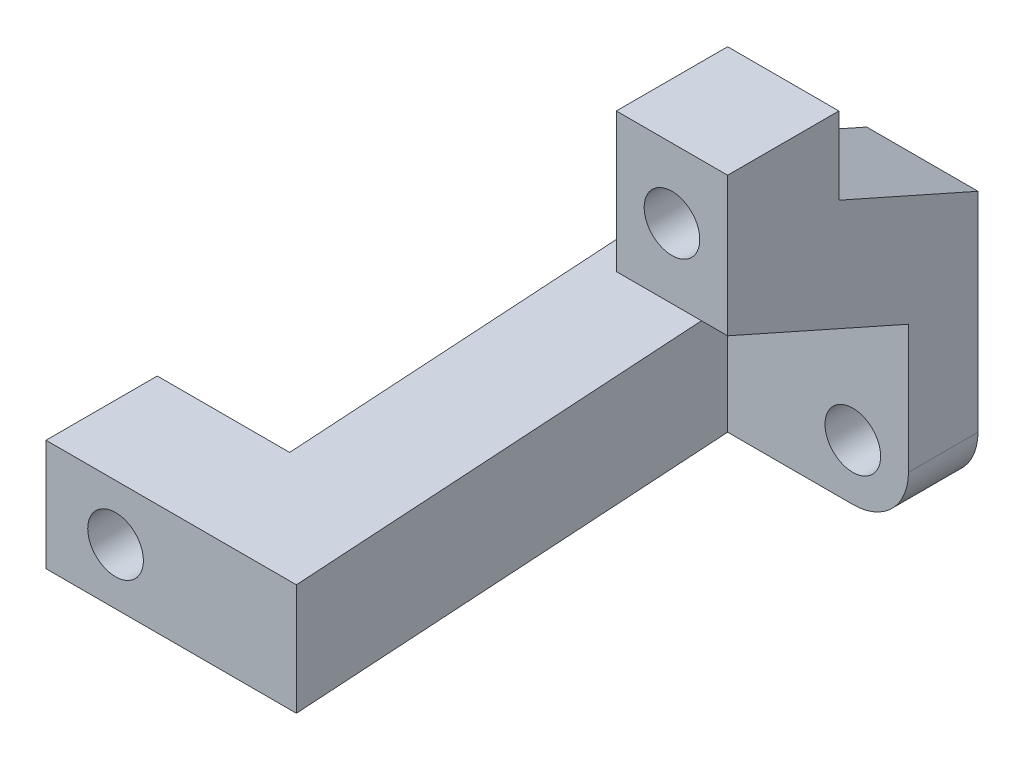
SolidWorks part; units mm, degrees
note: The reader was unsure of these and kept them because the rebuilt part matched: shared geometry of "草图1<6>", "草图1<7>".
ref_plane "前视基准面" through (0, 0, 0) normal (0, 0, 1) x (1, 0, 0)
ref_plane "上视基准面" through (0, 0, 0) normal (0, 1, 0) x (1, 0, 0)
ref_plane "右视基准面" through (0, 0, 0) normal (1, 0, 0) x (0, 0, -1)
sketch "草图1" plane through (0, 0, 0) normal (0, 0, 1) x (1, 0, 0)
  line L0 (-20, -4) -> (0, -4)
  line L1 (4, 20) -> (4, 0)
  line L2 (-20, 4) -> (-8, 4)
  line L3 (-4, 8) -> (-4, 20)
  line L4 (-15, -4) -> (-15, 4)
  line L5 (4, 15) -> (-4.7571, 15)
  circle A0 centre (-20, 0) radius 2
  arc A1 (-20, 4) -> (-20, -4) centre (-20, 0) ccw
  circle A3 centre (0, 0) radius 2
  arc A4 (4, 20) -> (-4, 20) centre (0, 20) ccw
  circle A5 centre (0, 20) radius 2
  arc A6 (0, -4) -> (4, 0) centre (0, 0) ccw
  arc A7 (-4, 8) -> (-8, 4) centre (-8, 8) cw
  dimension "D1" = 4
  dimension "D2" = 8
  dimension "D3" = 4
  dimension "D6" = 4
  dimension "D7" = 4
  dimension "D8" = 4
  dimension "D4" = 20
  dimension "D5" = 20
  dimension "D9" = 5
  dimension "D10" = 5
extrude "凸台-拉伸1" add sketch "草图1" along normal blind 5 contours L3 A7 L2 L4 L0 A6 L1 A4 A3 A5
sketch "草图2" plane through (0, 0, 0) normal (0, 0, 1) x (1, 0, 0)
  line L0 (-17, 4) -> (-17, -4)
  line L3 (-17, -4) -> (-25, -4)
  line L4 (-25, -4) -> (-25, 4)
  line L5 (-25, 4) -> (-17, 4)
  line L7 (4, 15) -> (4, 0) construction
  dimension "D1" = 21
  dimension "D2" = 8
ref_plane "基准面1" through (0, 0, 38) normal (0, 0, 1) x (1, 0, 0)
sketch "草图6" plane through (0, 0, 38) normal (0, 0, 1) x (1, 0, 0)
  line L13 (-7, 4) -> (-7, -4)
  line L14 (-15, -4) -> (-15, 4)
  line L15 (-15, 4) -> (-7, 4)
  line L16 (-7, -4) -> (-15, -4)
sketch "草图7" plane through (0, 0, 5) normal (0, 0, 1) x (1, 0, 0)
  line L0 (-15, -4) -> (0, -4) construction
  line L1 (-17, 4) -> (-9, 4)
  line L2 (-17, 4) -> (-17, -4)
  line L3 (-17, -4) -> (-9, -4)
  line L4 (-9, 4) -> (-9, -4)
  dimension "D1" = 8
loft "放样2" add profiles "草图7", "草图6"
ref_plane "基准面2" through (-25, 0, 0) normal (1, 0, 0) x (0, 0, -1)
sketch "草图9" plane through (-25, 0, 0) normal (1, 0, 0) x (0, 0, -1)
  line L0 (-5, 4) -> (-38, 4) construction
  line L1 (-30, 4) -> (-38, 4)
  line L2 (-30, 4) -> (-30, -4)
  line L3 (-30, -4) -> (-38, -4)
  line L4 (-38, 4) -> (-38, -4)
  line L5 (-38, 15.9501) -> (-38, -15.9501) construction
  line L6 (-5, -4) -> (-38, -4) construction
  dimension "D1" = 8
extrude "凸台-拉伸5" add sketch "草图9" along a picked direction on the side of the normal up to surface (10 mm away)
extrude "切除-拉伸2" cut sketch "草图1<6>" along normal blind 99 contours A0
sketch "草图1<6>" plane through (0, 0, 0) normal (0, 0, 1) x (1, 0, 0) same geometry as "草图1"
sketch "草图14" plane through (0, 0, 0) normal (0, 0, 1) x (1, 0, 0)
  line L0 (4, 15) -> (4, 0) construction
  line L1 (-4, 15) -> (4, 15)
  line L2 (-4, 15) -> (-4, 7)
  line L3 (-4, 7) -> (4, 7)
  line L4 (4, 15) -> (4, 7)
  dimension "D1" = 8
ref_plane "基准面3" through (0, 0, 18) normal (0, 0, 1) x (1, 0, 0)
sketch "草图15" plane through (0, 0, 18) normal (0, 0, 1) x (1, 0, 0)
  line L1 (-4, 15) -> (4, 15)
  line L2 (-4, 15) -> (-4, 23)
  line L3 (-4, 23) -> (4, 23)
  line L4 (4, 15) -> (4, 23)
  dimension "D1" = 8
  dimension "D2" = 8
loft "放样3" add profiles "草图14", "草图15"
ref_plane "基准面4" through (0, 25, 0) normal (0, 1, 0) x (1, 0, 0)
sketch "草图17" plane through (0, 25, 0) normal (0, 1, 0) x (1, 0, 0)
  line L0 (-15.9501, -18) -> (15.9501, -18) construction
  line L1 (-4, -18) -> (4, -18)
  line L2 (-4, -18) -> (-4, -10)
  line L3 (-4, -10) -> (4, -10)
  line L4 (4, -18) -> (4, -10)
  line L5 (-4, 0) -> (-4, -18) construction
  line L6 (4, 0) -> (4, -18) construction
  dimension "D1" = 8
extrude "凸台-拉伸7" add sketch "草图17" against normal up to surface (2 mm away)
extrude "切除-拉伸4" cut sketch "草图1<7>" along normal blind 33.5 contours A5
sketch "草图1<7>" plane through (0, 0, 0) normal (0, 0, 1) x (1, 0, 0) same geometry as "草图1"
